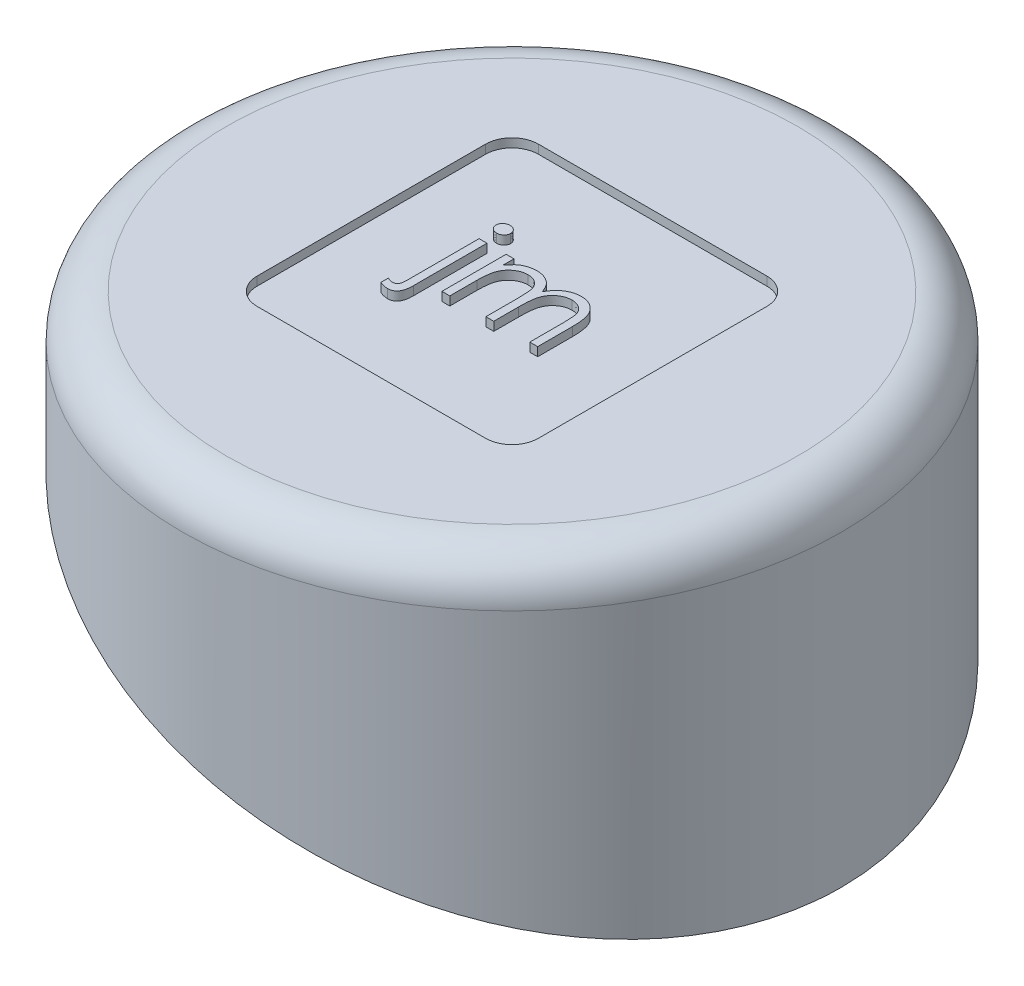
SolidWorks part; units mm, degrees
ref_plane "Front Plane" through (0, 0, 0) normal (0, 0, 1) x (1, 0, 0)
ref_plane "Top Plane" through (0, 0, 0) normal (0, 1, 0) x (1, 0, 0)
ref_plane "Right Plane" through (0, 0, 0) normal (1, 0, 0) x (0, 0, -1)
sketch "Sketch1" plane through (0, 0, 0) normal (0, 1, 0) x (1, 0, 0)
  circle A0 centre (0, 0) radius 37.5
  dimension "D1" = 75
extrude "Boss-Extrude1" add sketch "Sketch1" along normal blind 40
sketch "Sketch2" plane through (0, 0, 0) normal (0, 0, 1) x (1, 0, 0)
  line L0 (37.5, 0) -> (-37.5, 0)
  line L1 (-37.5, 0) -> (-37.5, 25.8246)
  line L2 (-37.5, 40) -> (-37.5, 0) construction
  line L3 (-37.5, 25.8246) -> (37.5, 0)
  dimension "D1" = 19
extrude "Cut-Extrude1" cut sketch "Sketch2" against normal up to body and the other way up to body separate body
fillet "Fillet1" radius 5 1 edges at (0, 40, 37.5)
shell "Shell1" thickness 2.5 removed face at (37.5, 0, 0)
sketch "Sketch3" plane through (0, 40, 0) normal (0, 1, 0) x (1, 0, 0)
  line L0 (0, -16) -> (0, -4) construction
  line L1 (-13, -16) -> (13, -16)
  line L2 (-16, -13) -> (-16, 13)
  line L3 (-13, 16) -> (13, 16)
  line L4 (16, -13) -> (16, 13)
  line L5 (-16, -16) -> (16, 16) construction
  line L6 (-16, 16) -> (16, -16) construction
  line L7 (-16, -4) -> (16, -4) construction
  arc A0 (13, 16) -> (16, 13) centre (13, 13) cw
  arc A1 (-16, 13) -> (-13, 16) centre (-13, 13) cw
  arc A2 (13, -16) -> (16, -13) centre (13, -13) ccw
  arc A3 (-13, -16) -> (-16, -13) centre (-13, -13) cw
  text T0 "jm" font "Century Gothic" height 10
  point P0 (0, 0)
  point P10 (0, 0)
  point P11 (0, -7.5413)
  point P13 (0, -4.8965)
  dimension "D3" = 3
  dimension "D4" = 3
  dimension "D1" = 32
  dimension "D2" = 12
extrude "Cut-Extrude2" cut sketch "Sketch3" against normal blind 1
